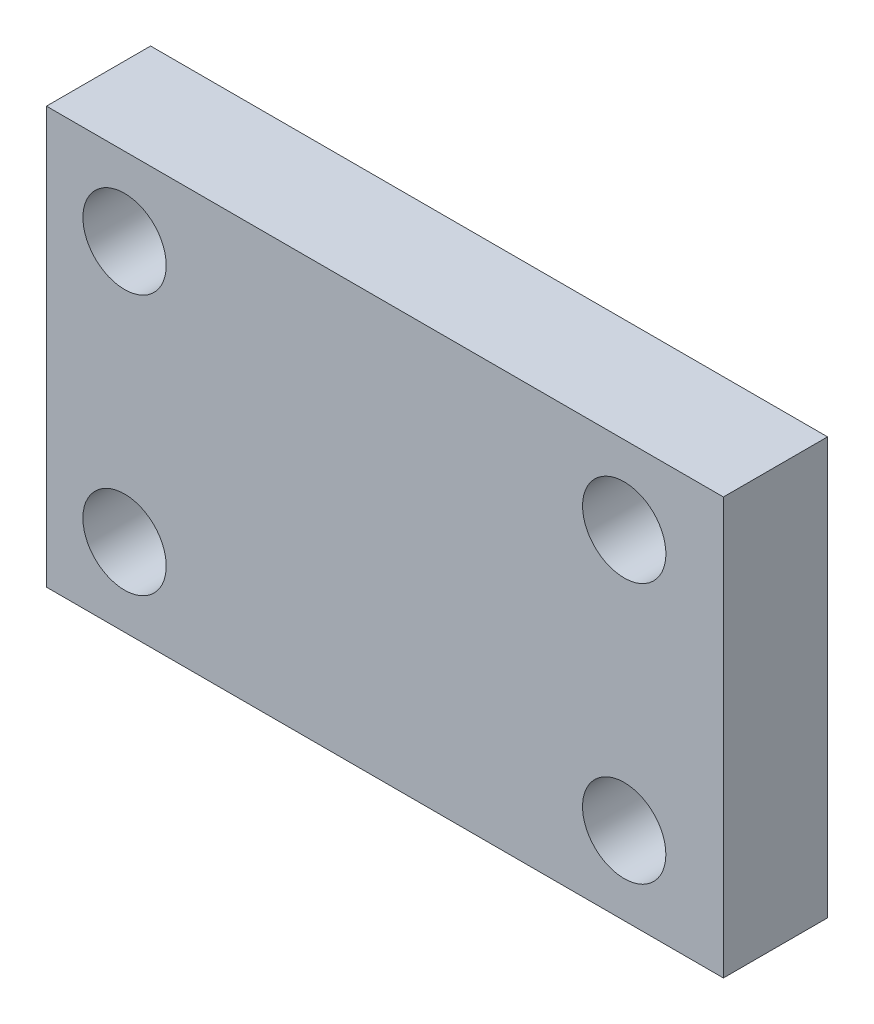
SolidWorks part; units mm, degrees
ref_plane "Plano frontal" through (0, 0, 0) normal (0, 0, 1) x (1, 0, 0)
ref_plane "Plano superior" through (0, 0, 0) normal (0, 1, 0) x (1, 0, 0)
ref_plane "Plano direito" through (0, 0, 0) normal (1, 0, 0) x (0, 0, -1)
sketch "Esboço3" plane through (0, 0, 0) normal (0, 0, 1) x (1, 0, 0)
  line L1 (-65, -40) -> (65, -40)
  line L2 (-65, -40) -> (-65, 40)
  line L3 (-65, 40) -> (65, 40)
  line L4 (65, -40) -> (65, 40)
  line L5 (-65, -40) -> (65, 40) construction
  line L6 (-65, 40) -> (65, -40) construction
  point P0 (0, 0)
  dimension "D1" = 80
  dimension "D2" = 130
extrude "Ressalto-extrusão2" add sketch "Esboço3" along normal blind 20
sketch "Esboço4" plane through (0, 0, 20) normal (0, 0, 1) x (1, 0, 0)
  line L0 (-84.0965, 0) -> (80.0436, 0) construction
  line L1 (-2.0265, 54.9791) -> (-2.0265, -52.4178) construction
  line L2 (-65, 40) -> (-65, -40) construction
  line L3 (65, 40) -> (-65, 40) construction
  circle A0 centre (-50, 25) radius 8
  circle A1 centre (45.9471, 25) radius 8
  circle A2 centre (45.9471, -25) radius 8
  circle A3 centre (-50, -25) radius 8
  dimension "D1" = 16
  dimension "D2" = 15
  dimension "D3" = 15
extrude "Corte-extrusão1" cut sketch "Esboço4" against normal blind 20
